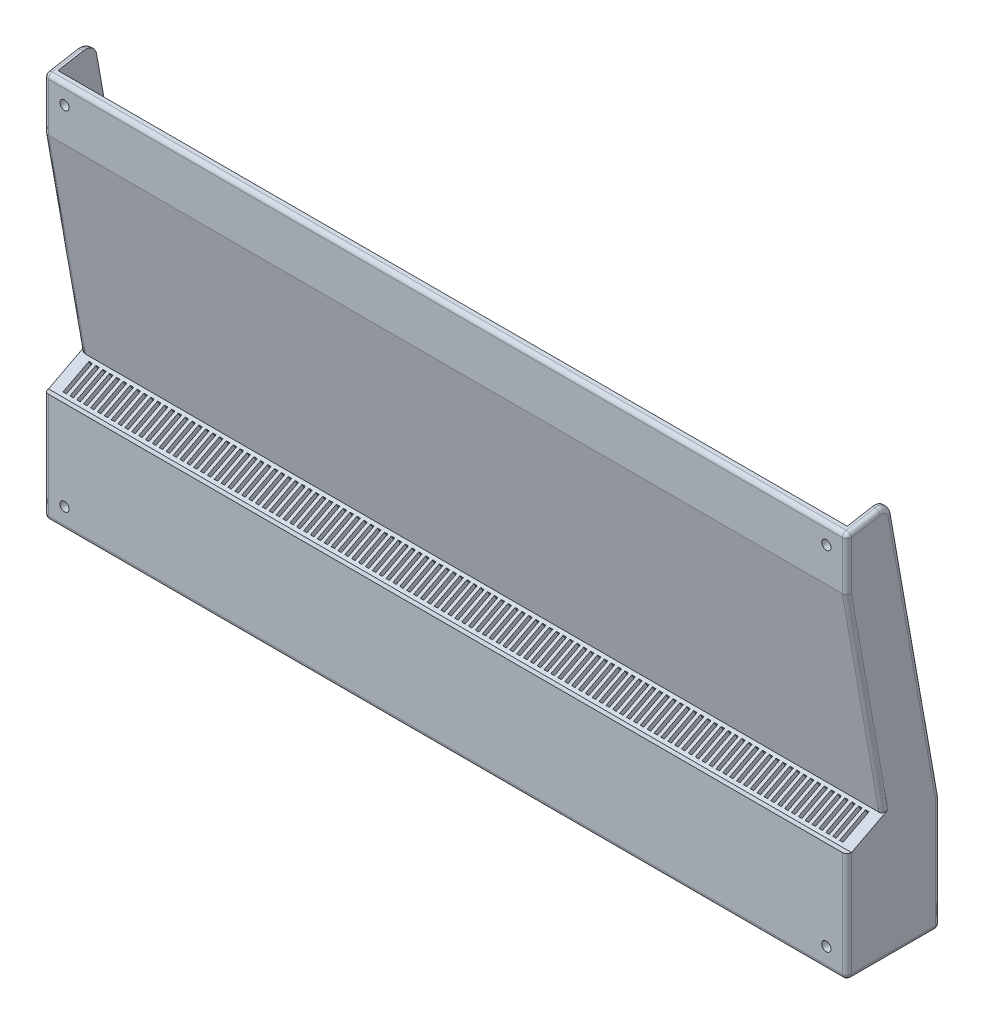
SolidWorks part; units mm, degrees
ref_plane "Front Plane" through (0, 0, 0) normal (0, 0, 1) x (1, 0, 0)
ref_plane "Top Plane" through (0, 0, 0) normal (0, 1, 0) x (1, 0, 0)
ref_plane "Right Plane" through (0, 0, 0) normal (1, 0, 0) x (0, 0, -1)
sketch "bottomplate" plane through (231.685, 0, 0) normal (1, 0, 0) x (0, 0, -1)
  line L0 (0, -72.0932) -> (-3.1401, -72.0932)
  line L1 (-3.1401, -72.0932) -> (-3.1401, 96.6415)
  line L2 (0, 97.1952) -> (11.0516, 99.1439) construction
  line L3 (-3.1401, 96.6415) -> (0, 97.1952)
  line L4 (0, 97.1952) -> (0, -72.0932)
  dimension "D1" = 0
extrude "B" add sketch "bottomplate" against normal up to surface (344.5411 mm away)
sketch "leftside" plane through (-112.8561, 0, 0) normal (-1, 0, 0) x (0, 0, 1)
  line L0 (3.1401, -72.0932) -> (-35.5061, -72.0932)
  line L2 (-37.5061, -70.0932) -> (-37.5061, -22.0932)
  line L3 (-37.5061, -22.0932) -> (-16.8439, 95.0881)
  line L5 (-11.0516, 99.1439) -> (3.1401, 96.6415)
  line L6 (3.1401, 96.6415) -> (3.1401, -72.0932)
  arc A0 (-35.5061, -72.0932) -> (-37.5061, -70.0932) centre (-35.5061, -70.0932) cw
  arc A1 (-11.0516, 99.1439) -> (-16.8439, 95.0881) centre (-11.9198, 94.2199) ccw
extrude "L" add sketch "leftside" along normal blind 3
sketch "rightside" plane through (231.685, 0, 0) normal (1, 0, 0) x (0, 0, -1)
  line L0 (-3.1401, -72.0932) -> (35.5061, -72.0932)
  line L2 (37.5061, -70.0932) -> (37.5061, -22.0932)
  line L3 (37.5061, -22.0932) -> (16.8439, 95.0881)
  line L5 (11.0516, 99.1439) -> (-3.1401, 96.6415)
  line L6 (-3.1401, 96.6415) -> (-3.1401, -72.0932)
  arc A0 (35.5061, -72.0932) -> (37.5061, -70.0932) centre (35.5061, -70.0932) ccw
  arc A1 (16.8439, 95.0881) -> (11.0516, 99.1439) centre (11.9198, 94.2199) ccw
extrude "R" add sketch "rightside" along normal blind 3
fillet "Fillet1" radius 2 2 edges at (59.4145, -72.0932, 3.1401) (59.4145, 96.6415, 3.1401)
fillet "Fillet2" radius 2 18 edges at (234.685, 36.4975, -27.175) (234.685, 98.3156, -14.7877) (234.685, 98.0384, -4.7821) (234.685, 96.2489, 2.6722) (234.685, -46.0932, -37.5061) (234.685, -71.5074, -36.9203) (234.685, -72.0932, -17.183) (234.685, -71.5074, 2.5543) (-115.8561, -46.0932, -37.5061) (-115.8561, -71.5074, -36.9203) (-115.8561, -72.0932, -17.183) (-115.8561, -71.5074, 2.5543) (-115.8561, 36.4975, -27.175) (-115.8561, 98.3156, -14.7877) (-115.8561, 98.0384, -4.7821) (-115.8561, 96.2489, 2.6722) (234.685, 12.4351, 3.1401) (-115.8561, 12.4351, 3.1401)
sketch "holes" plane through (0, 0, 3.1401) normal (0, 0, 1) x (1, 0, 0)
  circle A0 centre (225.685, -63.0932) radius 2
  circle A1 centre (225.685, 88.6699) radius 2
  circle A2 centre (-106.8561, 88.6699) radius 2
  circle A3 centre (-106.8561, -63.0932) radius 2
extrude "Cut-Extrude1" cut sketch "holes" against normal blind 6.5
sketch "Sketch3" plane through (-115.8561, 0, 0) normal (-1, 0, 0) x (0, 0, 1)
  line L0 (-16.9697, -14.7016) -> (-1.3669, 73.7862)
  line L1 (-16.9697, -14.7016) -> (1.1401, -24.0977)
  line L3 (1.1401, -70.0932) -> (1.1401, 94.9633) construction
  line L4 (-1.3669, 73.7862) -> (6.335, 73.7862)
  line L5 (6.335, 73.7862) -> (6.335, -24.0977)
  line L6 (6.335, -24.0977) -> (1.1401, -24.0977)
  line L7 (-5.393, 85.4533) -> (-22.5841, -12.0427) construction
  point P2 (1.1401, 73.822)
  point P10 (1.1401, -23.3058)
  point P11 (6.335, -24.0977)
  point P12 (1.1401, 73.824)
extrude "Cut-Extrude2" cut sketch "Sketch3" against normal up to surface (350.5411 mm away) up to face at (234.685, 20.8573, -15.9182)
sketch "Sketch7" plane through (0, 73.7862, 0) normal (0, -1, 0) x (1, 0, 0)
  line L0 (-112.8561, -1.3669) -> (-115.8561, -1.3669)
  line L1 (-115.8561, -1.3669) -> (-115.8561, 1.1401)
  line L3 (-113.8561, 3.1401) -> (232.685, 3.1401)
  line L4 (232.685, 1.1401) -> (232.685, 3.1401) construction
  line L6 (234.685, 1.1401) -> (234.685, -1.3669)
  line L7 (234.685, -1.3669) -> (231.685, -1.3669)
  line L8 (231.685, -1.3669) -> (231.685, 0)
  line L9 (231.685, 0) -> (-112.8561, 0)
  line L10 (-112.8561, 0) -> (-112.8561, -1.3669)
  arc A0 (234.685, 1.1401) -> (232.685, 3.1401) centre (232.685, 1.1401) ccw construction
  arc A1 (-115.8561, 1.1401) -> (-113.8561, 3.1401) centre (-113.8561, 1.1401) cw
  arc A2 (232.685, 3.1401) -> (234.685, 1.1401) centre (232.685, 1.1401) cw
extrude "Boss-Extrude1" add sketch "Sketch7" along direction (0, -0.9848, -0.1736) on the side of the normal blind 92.5
sketch "Sketch9" plane through (0, 0, 0) normal (0, 0, -1) x (-1, 0, 0)
  line L0 (112.8561, -23.5062) -> (-231.685, -23.5062)
  line L1 (-231.685, -23.5062) -> (-231.685, -26.5062)
  line L2 (-231.685, -72.0932) -> (-231.685, -23.5062) construction
  line L3 (-231.685, -26.5062) -> (112.8561, -26.5062)
  line L4 (112.8561, -72.0932) -> (112.8561, -23.5062) construction
  line L5 (112.8561, -26.5062) -> (112.8561, -23.5062)
  dimension "D1" = 3
extrude "Boss-Extrude2" add sketch "Sketch9" along direction (0, 0.4605, -0.8876) on the side of the normal up to surface (18.253 mm away) up to face at (59.4145, 28.2389, -8.0312)
sketch "Sketch10" plane through (0, -18.5205, -9.6093) normal (0, 0.8876, 0.4605) x (1, 0, 0)
  line L0 (-113.8561, 3.6402) -> (232.685, 3.6402) construction
  line L1 (-110.8561, -10.6101) -> (-109.3561, -10.6101)
  line L2 (-110.8561, -10.6101) -> (-110.8561, 2.1402)
  line L3 (-110.8561, 2.1402) -> (-109.3561, 2.1402)
  line L4 (-109.3561, -10.6101) -> (-109.3561, 2.1402)
  line L5 (234.685, -12.1101) -> (-115.8561, -12.1101) construction
  line L6 (-115.8561, 5.7046) -> (-115.8561, -12.1101) construction
  line L7 (-107.8561, -10.6101) -> (-107.8561, 2.1402)
  line L8 (-107.8561, -10.6101) -> (-106.3561, -10.6101)
  line L9 (-106.3561, -10.6101) -> (-106.3561, 2.1402)
  line L10 (-107.8561, 2.1402) -> (-106.3561, 2.1402)
  line L11 (-104.8561, -10.6101) -> (-104.8561, 2.1402)
  line L12 (-104.8561, -10.6101) -> (-103.3561, -10.6101)
  line L13 (-103.3561, -10.6101) -> (-103.3561, 2.1402)
  line L14 (-104.8561, 2.1402) -> (-103.3561, 2.1402)
  line L15 (-101.8561, -10.6101) -> (-101.8561, 2.1402)
  line L16 (-101.8561, -10.6101) -> (-100.3561, -10.6101)
  line L17 (-100.3561, -10.6101) -> (-100.3561, 2.1402)
  line L18 (-101.8561, 2.1402) -> (-100.3561, 2.1402)
  line L19 (-98.8561, -10.6101) -> (-98.8561, 2.1402)
  line L20 (-98.8561, -10.6101) -> (-97.3561, -10.6101)
  line L21 (-97.3561, -10.6101) -> (-97.3561, 2.1402)
  line L22 (-98.8561, 2.1402) -> (-97.3561, 2.1402)
  line L23 (-95.8561, -10.6101) -> (-95.8561, 2.1402)
  line L24 (-95.8561, -10.6101) -> (-94.3561, -10.6101)
  line L25 (-94.3561, -10.6101) -> (-94.3561, 2.1402)
  line L26 (-95.8561, 2.1402) -> (-94.3561, 2.1402)
  line L27 (-92.8561, -10.6101) -> (-92.8561, 2.1402)
  line L28 (-92.8561, -10.6101) -> (-91.3561, -10.6101)
  line L29 (-91.3561, -10.6101) -> (-91.3561, 2.1402)
  line L30 (-92.8561, 2.1402) -> (-91.3561, 2.1402)
  line L31 (-89.8561, -10.6101) -> (-89.8561, 2.1402)
  line L32 (-89.8561, -10.6101) -> (-88.3561, -10.6101)
  line L33 (-88.3561, -10.6101) -> (-88.3561, 2.1402)
  line L34 (-89.8561, 2.1402) -> (-88.3561, 2.1402)
  line L35 (-86.8561, -10.6101) -> (-86.8561, 2.1402)
  line L36 (-86.8561, -10.6101) -> (-85.3561, -10.6101)
  line L37 (-85.3561, -10.6101) -> (-85.3561, 2.1402)
  line L38 (-86.8561, 2.1402) -> (-85.3561, 2.1402)
  line L39 (-83.8561, -10.6101) -> (-83.8561, 2.1402)
  line L40 (-83.8561, -10.6101) -> (-82.3561, -10.6101)
  line L41 (-82.3561, -10.6101) -> (-82.3561, 2.1402)
  line L42 (-83.8561, 2.1402) -> (-82.3561, 2.1402)
  line L43 (-80.8561, -10.6101) -> (-80.8561, 2.1402)
  line L44 (-80.8561, -10.6101) -> (-79.3561, -10.6101)
  line L45 (-79.3561, -10.6101) -> (-79.3561, 2.1402)
  line L46 (-80.8561, 2.1402) -> (-79.3561, 2.1402)
  line L47 (-77.8561, -10.6101) -> (-77.8561, 2.1402)
  line L48 (-77.8561, -10.6101) -> (-76.3561, -10.6101)
  line L49 (-76.3561, -10.6101) -> (-76.3561, 2.1402)
  line L50 (-77.8561, 2.1402) -> (-76.3561, 2.1402)
  line L51 (-74.8561, -10.6101) -> (-74.8561, 2.1402)
  line L52 (-74.8561, -10.6101) -> (-73.3561, -10.6101)
  line L53 (-73.3561, -10.6101) -> (-73.3561, 2.1402)
  line L54 (-74.8561, 2.1402) -> (-73.3561, 2.1402)
  line L55 (-71.8561, -10.6101) -> (-71.8561, 2.1402)
  line L56 (-71.8561, -10.6101) -> (-70.3561, -10.6101)
  line L57 (-70.3561, -10.6101) -> (-70.3561, 2.1402)
  line L58 (-71.8561, 2.1402) -> (-70.3561, 2.1402)
  line L59 (-68.8561, -10.6101) -> (-68.8561, 2.1402)
  line L60 (-68.8561, -10.6101) -> (-67.3561, -10.6101)
  line L61 (-67.3561, -10.6101) -> (-67.3561, 2.1402)
  line L62 (-68.8561, 2.1402) -> (-67.3561, 2.1402)
  line L63 (-65.8561, -10.6101) -> (-65.8561, 2.1402)
  line L64 (-65.8561, -10.6101) -> (-64.3561, -10.6101)
  line L65 (-64.3561, -10.6101) -> (-64.3561, 2.1402)
  line L66 (-65.8561, 2.1402) -> (-64.3561, 2.1402)
  line L67 (-62.8561, -10.6101) -> (-62.8561, 2.1402)
  line L68 (-62.8561, -10.6101) -> (-61.3561, -10.6101)
  line L69 (-61.3561, -10.6101) -> (-61.3561, 2.1402)
  line L70 (-62.8561, 2.1402) -> (-61.3561, 2.1402)
  line L71 (-59.8561, -10.6101) -> (-59.8561, 2.1402)
  line L72 (-59.8561, -10.6101) -> (-58.3561, -10.6101)
  line L73 (-58.3561, -10.6101) -> (-58.3561, 2.1402)
  line L74 (-59.8561, 2.1402) -> (-58.3561, 2.1402)
  line L75 (-56.8561, -10.6101) -> (-56.8561, 2.1402)
  line L76 (-56.8561, -10.6101) -> (-55.3561, -10.6101)
  line L77 (-55.3561, -10.6101) -> (-55.3561, 2.1402)
  line L78 (-56.8561, 2.1402) -> (-55.3561, 2.1402)
  line L79 (-53.8561, -10.6101) -> (-53.8561, 2.1402)
  line L80 (-53.8561, -10.6101) -> (-52.3561, -10.6101)
  line L81 (-52.3561, -10.6101) -> (-52.3561, 2.1402)
  line L82 (-53.8561, 2.1402) -> (-52.3561, 2.1402)
  line L83 (-50.8561, -10.6101) -> (-50.8561, 2.1402)
  line L84 (-50.8561, -10.6101) -> (-49.3561, -10.6101)
  line L85 (-49.3561, -10.6101) -> (-49.3561, 2.1402)
  line L86 (-50.8561, 2.1402) -> (-49.3561, 2.1402)
  line L87 (-47.8561, -10.6101) -> (-47.8561, 2.1402)
  line L88 (-47.8561, -10.6101) -> (-46.3561, -10.6101)
  line L89 (-46.3561, -10.6101) -> (-46.3561, 2.1402)
  line L90 (-47.8561, 2.1402) -> (-46.3561, 2.1402)
  line L91 (-44.8561, -10.6101) -> (-44.8561, 2.1402)
  line L92 (-44.8561, -10.6101) -> (-43.3561, -10.6101)
  line L93 (-43.3561, -10.6101) -> (-43.3561, 2.1402)
  line L94 (-44.8561, 2.1402) -> (-43.3561, 2.1402)
  line L95 (-41.8561, -10.6101) -> (-41.8561, 2.1402)
  line L96 (-41.8561, -10.6101) -> (-40.3561, -10.6101)
  line L97 (-40.3561, -10.6101) -> (-40.3561, 2.1402)
  line L98 (-41.8561, 2.1402) -> (-40.3561, 2.1402)
  line L99 (-38.8561, -10.6101) -> (-38.8561, 2.1402)
  line L100 (-38.8561, -10.6101) -> (-37.3561, -10.6101)
  line L101 (-37.3561, -10.6101) -> (-37.3561, 2.1402)
  line L102 (-38.8561, 2.1402) -> (-37.3561, 2.1402)
  line L103 (-35.8561, -10.6101) -> (-35.8561, 2.1402)
  line L104 (-35.8561, -10.6101) -> (-34.3561, -10.6101)
  line L105 (-34.3561, -10.6101) -> (-34.3561, 2.1402)
  line L106 (-35.8561, 2.1402) -> (-34.3561, 2.1402)
  line L107 (-32.8561, -10.6101) -> (-32.8561, 2.1402)
  line L108 (-32.8561, -10.6101) -> (-31.3561, -10.6101)
  line L109 (-31.3561, -10.6101) -> (-31.3561, 2.1402)
  line L110 (-32.8561, 2.1402) -> (-31.3561, 2.1402)
  line L111 (-29.8561, -10.6101) -> (-29.8561, 2.1402)
  line L112 (-29.8561, -10.6101) -> (-28.3561, -10.6101)
  line L113 (-28.3561, -10.6101) -> (-28.3561, 2.1402)
  line L114 (-29.8561, 2.1402) -> (-28.3561, 2.1402)
  line L115 (-26.8561, -10.6101) -> (-26.8561, 2.1402)
  line L116 (-26.8561, -10.6101) -> (-25.3561, -10.6101)
  line L117 (-25.3561, -10.6101) -> (-25.3561, 2.1402)
  line L118 (-26.8561, 2.1402) -> (-25.3561, 2.1402)
  line L119 (-23.8561, -10.6101) -> (-23.8561, 2.1402)
  line L120 (-23.8561, -10.6101) -> (-22.3561, -10.6101)
  line L121 (-22.3561, -10.6101) -> (-22.3561, 2.1402)
  line L122 (-23.8561, 2.1402) -> (-22.3561, 2.1402)
  line L123 (-20.8561, -10.6101) -> (-20.8561, 2.1402)
  line L124 (-20.8561, -10.6101) -> (-19.3561, -10.6101)
  line L125 (-19.3561, -10.6101) -> (-19.3561, 2.1402)
  line L126 (-20.8561, 2.1402) -> (-19.3561, 2.1402)
  line L127 (-17.8561, -10.6101) -> (-17.8561, 2.1402)
  line L128 (-17.8561, -10.6101) -> (-16.3561, -10.6101)
  line L129 (-16.3561, -10.6101) -> (-16.3561, 2.1402)
  line L130 (-17.8561, 2.1402) -> (-16.3561, 2.1402)
  line L131 (-14.8561, -10.6101) -> (-14.8561, 2.1402)
  line L132 (-14.8561, -10.6101) -> (-13.3561, -10.6101)
  line L133 (-13.3561, -10.6101) -> (-13.3561, 2.1402)
  line L134 (-14.8561, 2.1402) -> (-13.3561, 2.1402)
  line L135 (-11.8561, -10.6101) -> (-11.8561, 2.1402)
  line L136 (-11.8561, -10.6101) -> (-10.3561, -10.6101)
  line L137 (-10.3561, -10.6101) -> (-10.3561, 2.1402)
  line L138 (-11.8561, 2.1402) -> (-10.3561, 2.1402)
  line L139 (-8.8561, -10.6101) -> (-8.8561, 2.1402)
  line L140 (-8.8561, -10.6101) -> (-7.3561, -10.6101)
  line L141 (-7.3561, -10.6101) -> (-7.3561, 2.1402)
  line L142 (-8.8561, 2.1402) -> (-7.3561, 2.1402)
  line L143 (-5.8561, -10.6101) -> (-5.8561, 2.1402)
  line L144 (-5.8561, -10.6101) -> (-4.3561, -10.6101)
  line L145 (-4.3561, -10.6101) -> (-4.3561, 2.1402)
  line L146 (-5.8561, 2.1402) -> (-4.3561, 2.1402)
  line L147 (-2.8561, -10.6101) -> (-2.8561, 2.1402)
  line L148 (-2.8561, -10.6101) -> (-1.3561, -10.6101)
  line L149 (-1.3561, -10.6101) -> (-1.3561, 2.1402)
  line L150 (-2.8561, 2.1402) -> (-1.3561, 2.1402)
  line L151 (0.1439, -10.6101) -> (0.1439, 2.1402)
  line L152 (0.1439, -10.6101) -> (1.6439, -10.6101)
  line L153 (1.6439, -10.6101) -> (1.6439, 2.1402)
  line L154 (0.1439, 2.1402) -> (1.6439, 2.1402)
  line L155 (3.1439, -10.6101) -> (3.1439, 2.1402)
  line L156 (3.1439, -10.6101) -> (4.6439, -10.6101)
  line L157 (4.6439, -10.6101) -> (4.6439, 2.1402)
  line L158 (3.1439, 2.1402) -> (4.6439, 2.1402)
  line L159 (6.1439, -10.6101) -> (6.1439, 2.1402)
  line L160 (6.1439, -10.6101) -> (7.6439, -10.6101)
  line L161 (7.6439, -10.6101) -> (7.6439, 2.1402)
  line L162 (6.1439, 2.1402) -> (7.6439, 2.1402)
  line L163 (9.1439, -10.6101) -> (9.1439, 2.1402)
  line L164 (9.1439, -10.6101) -> (10.6439, -10.6101)
  line L165 (10.6439, -10.6101) -> (10.6439, 2.1402)
  line L166 (9.1439, 2.1402) -> (10.6439, 2.1402)
  line L167 (12.1439, -10.6101) -> (12.1439, 2.1402)
  line L168 (12.1439, -10.6101) -> (13.6439, -10.6101)
  line L169 (13.6439, -10.6101) -> (13.6439, 2.1402)
  line L170 (12.1439, 2.1402) -> (13.6439, 2.1402)
  line L171 (15.1439, -10.6101) -> (15.1439, 2.1402)
  line L172 (15.1439, -10.6101) -> (16.6439, -10.6101)
  line L173 (16.6439, -10.6101) -> (16.6439, 2.1402)
  line L174 (15.1439, 2.1402) -> (16.6439, 2.1402)
  line L175 (18.1439, -10.6101) -> (18.1439, 2.1402)
  line L176 (18.1439, -10.6101) -> (19.6439, -10.6101)
  line L177 (19.6439, -10.6101) -> (19.6439, 2.1402)
  line L178 (18.1439, 2.1402) -> (19.6439, 2.1402)
  line L179 (21.1439, -10.6101) -> (21.1439, 2.1402)
  line L180 (21.1439, -10.6101) -> (22.6439, -10.6101)
  line L181 (22.6439, -10.6101) -> (22.6439, 2.1402)
  line L182 (21.1439, 2.1402) -> (22.6439, 2.1402)
  line L183 (24.1439, -10.6101) -> (24.1439, 2.1402)
  line L184 (24.1439, -10.6101) -> (25.6439, -10.6101)
  line L185 (25.6439, -10.6101) -> (25.6439, 2.1402)
  line L186 (24.1439, 2.1402) -> (25.6439, 2.1402)
  line L187 (27.1439, -10.6101) -> (27.1439, 2.1402)
  line L188 (27.1439, -10.6101) -> (28.6439, -10.6101)
  line L189 (28.6439, -10.6101) -> (28.6439, 2.1402)
  line L190 (27.1439, 2.1402) -> (28.6439, 2.1402)
  line L191 (30.1439, -10.6101) -> (30.1439, 2.1402)
  line L192 (30.1439, -10.6101) -> (31.6439, -10.6101)
  line L193 (31.6439, -10.6101) -> (31.6439, 2.1402)
  line L194 (30.1439, 2.1402) -> (31.6439, 2.1402)
  line L195 (33.1439, -10.6101) -> (33.1439, 2.1402)
  line L196 (33.1439, -10.6101) -> (34.6439, -10.6101)
  line L197 (34.6439, -10.6101) -> (34.6439, 2.1402)
  line L198 (33.1439, 2.1402) -> (34.6439, 2.1402)
  line L199 (36.1439, -10.6101) -> (36.1439, 2.1402)
  line L200 (36.1439, -10.6101) -> (37.6439, -10.6101)
  line L201 (37.6439, -10.6101) -> (37.6439, 2.1402)
  line L202 (36.1439, 2.1402) -> (37.6439, 2.1402)
  line L203 (39.1439, -10.6101) -> (39.1439, 2.1402)
  line L204 (39.1439, -10.6101) -> (40.6439, -10.6101)
  line L205 (40.6439, -10.6101) -> (40.6439, 2.1402)
  line L206 (39.1439, 2.1402) -> (40.6439, 2.1402)
  line L207 (42.1439, -10.6101) -> (42.1439, 2.1402)
  line L208 (42.1439, -10.6101) -> (43.6439, -10.6101)
  line L209 (43.6439, -10.6101) -> (43.6439, 2.1402)
  line L210 (42.1439, 2.1402) -> (43.6439, 2.1402)
  line L211 (45.1439, -10.6101) -> (45.1439, 2.1402)
  line L212 (45.1439, -10.6101) -> (46.6439, -10.6101)
  line L213 (46.6439, -10.6101) -> (46.6439, 2.1402)
  line L214 (45.1439, 2.1402) -> (46.6439, 2.1402)
  line L215 (48.1439, -10.6101) -> (48.1439, 2.1402)
  line L216 (48.1439, -10.6101) -> (49.6439, -10.6101)
  line L217 (49.6439, -10.6101) -> (49.6439, 2.1402)
  line L218 (48.1439, 2.1402) -> (49.6439, 2.1402)
  line L219 (51.1439, -10.6101) -> (51.1439, 2.1402)
  line L220 (51.1439, -10.6101) -> (52.6439, -10.6101)
  line L221 (52.6439, -10.6101) -> (52.6439, 2.1402)
  line L222 (51.1439, 2.1402) -> (52.6439, 2.1402)
  line L223 (54.1439, -10.6101) -> (54.1439, 2.1402)
  line L224 (54.1439, -10.6101) -> (55.6439, -10.6101)
  line L225 (55.6439, -10.6101) -> (55.6439, 2.1402)
  line L226 (54.1439, 2.1402) -> (55.6439, 2.1402)
  line L227 (57.1439, -10.6101) -> (57.1439, 2.1402)
  line L228 (57.1439, -10.6101) -> (58.6439, -10.6101)
  line L229 (58.6439, -10.6101) -> (58.6439, 2.1402)
  line L230 (57.1439, 2.1402) -> (58.6439, 2.1402)
  line L231 (60.1439, -10.6101) -> (60.1439, 2.1402)
  line L232 (60.1439, -10.6101) -> (61.6439, -10.6101)
  line L233 (61.6439, -10.6101) -> (61.6439, 2.1402)
  line L234 (60.1439, 2.1402) -> (61.6439, 2.1402)
  line L235 (63.1439, -10.6101) -> (63.1439, 2.1402)
  line L236 (63.1439, -10.6101) -> (64.6439, -10.6101)
  line L237 (64.6439, -10.6101) -> (64.6439, 2.1402)
  line L238 (63.1439, 2.1402) -> (64.6439, 2.1402)
  line L239 (66.1439, -10.6101) -> (66.1439, 2.1402)
  line L240 (66.1439, -10.6101) -> (67.6439, -10.6101)
  line L241 (67.6439, -10.6101) -> (67.6439, 2.1402)
  line L242 (66.1439, 2.1402) -> (67.6439, 2.1402)
  line L243 (69.1439, -10.6101) -> (69.1439, 2.1402)
  line L244 (69.1439, -10.6101) -> (70.6439, -10.6101)
  line L245 (70.6439, -10.6101) -> (70.6439, 2.1402)
  line L246 (69.1439, 2.1402) -> (70.6439, 2.1402)
  line L247 (72.1439, -10.6101) -> (72.1439, 2.1402)
  line L248 (72.1439, -10.6101) -> (73.6439, -10.6101)
  line L249 (73.6439, -10.6101) -> (73.6439, 2.1402)
  line L250 (72.1439, 2.1402) -> (73.6439, 2.1402)
  line L251 (75.1439, -10.6101) -> (75.1439, 2.1402)
  line L252 (75.1439, -10.6101) -> (76.6439, -10.6101)
  line L253 (76.6439, -10.6101) -> (76.6439, 2.1402)
  line L254 (75.1439, 2.1402) -> (76.6439, 2.1402)
  line L255 (78.1439, -10.6101) -> (78.1439, 2.1402)
  line L256 (78.1439, -10.6101) -> (79.6439, -10.6101)
  line L257 (79.6439, -10.6101) -> (79.6439, 2.1402)
  line L258 (78.1439, 2.1402) -> (79.6439, 2.1402)
  line L259 (81.1439, -10.6101) -> (81.1439, 2.1402)
  line L260 (81.1439, -10.6101) -> (82.6439, -10.6101)
  line L261 (82.6439, -10.6101) -> (82.6439, 2.1402)
  line L262 (81.1439, 2.1402) -> (82.6439, 2.1402)
  line L263 (84.1439, -10.6101) -> (84.1439, 2.1402)
  line L264 (84.1439, -10.6101) -> (85.6439, -10.6101)
  line L265 (85.6439, -10.6101) -> (85.6439, 2.1402)
  line L266 (84.1439, 2.1402) -> (85.6439, 2.1402)
  line L267 (87.1439, -10.6101) -> (87.1439, 2.1402)
  line L268 (87.1439, -10.6101) -> (88.6439, -10.6101)
  line L269 (88.6439, -10.6101) -> (88.6439, 2.1402)
  line L270 (87.1439, 2.1402) -> (88.6439, 2.1402)
  line L271 (90.1439, -10.6101) -> (90.1439, 2.1402)
  line L272 (90.1439, -10.6101) -> (91.6439, -10.6101)
  line L273 (91.6439, -10.6101) -> (91.6439, 2.1402)
  line L274 (90.1439, 2.1402) -> (91.6439, 2.1402)
  line L275 (93.1439, -10.6101) -> (93.1439, 2.1402)
  line L276 (93.1439, -10.6101) -> (94.6439, -10.6101)
  line L277 (94.6439, -10.6101) -> (94.6439, 2.1402)
  line L278 (93.1439, 2.1402) -> (94.6439, 2.1402)
  line L279 (96.1439, -10.6101) -> (96.1439, 2.1402)
  line L280 (96.1439, -10.6101) -> (97.6439, -10.6101)
  line L281 (97.6439, -10.6101) -> (97.6439, 2.1402)
  line L282 (96.1439, 2.1402) -> (97.6439, 2.1402)
  line L283 (99.1439, -10.6101) -> (99.1439, 2.1402)
  line L284 (99.1439, -10.6101) -> (100.6439, -10.6101)
  line L285 (100.6439, -10.6101) -> (100.6439, 2.1402)
  line L286 (99.1439, 2.1402) -> (100.6439, 2.1402)
  line L287 (102.1439, -10.6101) -> (102.1439, 2.1402)
  line L288 (102.1439, -10.6101) -> (103.6439, -10.6101)
  line L289 (103.6439, -10.6101) -> (103.6439, 2.1402)
  line L290 (102.1439, 2.1402) -> (103.6439, 2.1402)
  line L291 (105.1439, -10.6101) -> (105.1439, 2.1402)
  line L292 (105.1439, -10.6101) -> (106.6439, -10.6101)
  line L293 (106.6439, -10.6101) -> (106.6439, 2.1402)
  line L294 (105.1439, 2.1402) -> (106.6439, 2.1402)
  line L295 (108.1439, -10.6101) -> (108.1439, 2.1402)
  line L296 (108.1439, -10.6101) -> (109.6439, -10.6101)
  line L297 (109.6439, -10.6101) -> (109.6439, 2.1402)
  line L298 (108.1439, 2.1402) -> (109.6439, 2.1402)
  line L299 (111.1439, -10.6101) -> (111.1439, 2.1402)
  line L300 (111.1439, -10.6101) -> (112.6439, -10.6101)
  line L301 (112.6439, -10.6101) -> (112.6439, 2.1402)
  line L302 (111.1439, 2.1402) -> (112.6439, 2.1402)
  line L303 (114.1439, -10.6101) -> (114.1439, 2.1402)
  line L304 (114.1439, -10.6101) -> (115.6439, -10.6101)
  line L305 (115.6439, -10.6101) -> (115.6439, 2.1402)
  line L306 (114.1439, 2.1402) -> (115.6439, 2.1402)
  line L307 (117.1439, -10.6101) -> (117.1439, 2.1402)
  line L308 (117.1439, -10.6101) -> (118.6439, -10.6101)
  line L309 (118.6439, -10.6101) -> (118.6439, 2.1402)
  line L310 (117.1439, 2.1402) -> (118.6439, 2.1402)
  line L311 (120.1439, -10.6101) -> (120.1439, 2.1402)
  line L312 (120.1439, -10.6101) -> (121.6439, -10.6101)
  line L313 (121.6439, -10.6101) -> (121.6439, 2.1402)
  line L314 (120.1439, 2.1402) -> (121.6439, 2.1402)
  line L315 (123.1439, -10.6101) -> (123.1439, 2.1402)
  line L316 (123.1439, -10.6101) -> (124.6439, -10.6101)
  line L317 (124.6439, -10.6101) -> (124.6439, 2.1402)
  line L318 (123.1439, 2.1402) -> (124.6439, 2.1402)
  line L319 (126.1439, -10.6101) -> (126.1439, 2.1402)
  line L320 (126.1439, -10.6101) -> (127.6439, -10.6101)
  line L321 (127.6439, -10.6101) -> (127.6439, 2.1402)
  line L322 (126.1439, 2.1402) -> (127.6439, 2.1402)
  line L323 (129.1439, -10.6101) -> (129.1439, 2.1402)
  line L324 (129.1439, -10.6101) -> (130.6439, -10.6101)
  line L325 (130.6439, -10.6101) -> (130.6439, 2.1402)
  line L326 (129.1439, 2.1402) -> (130.6439, 2.1402)
  line L327 (132.1439, -10.6101) -> (132.1439, 2.1402)
  line L328 (132.1439, -10.6101) -> (133.6439, -10.6101)
  line L329 (133.6439, -10.6101) -> (133.6439, 2.1402)
  line L330 (132.1439, 2.1402) -> (133.6439, 2.1402)
  line L331 (135.1439, -10.6101) -> (135.1439, 2.1402)
  line L332 (135.1439, -10.6101) -> (136.6439, -10.6101)
  line L333 (136.6439, -10.6101) -> (136.6439, 2.1402)
  line L334 (135.1439, 2.1402) -> (136.6439, 2.1402)
  line L335 (138.1439, -10.6101) -> (138.1439, 2.1402)
  line L336 (138.1439, -10.6101) -> (139.6439, -10.6101)
  line L337 (139.6439, -10.6101) -> (139.6439, 2.1402)
  line L338 (138.1439, 2.1402) -> (139.6439, 2.1402)
  line L339 (141.1439, -10.6101) -> (141.1439, 2.1402)
  line L340 (141.1439, -10.6101) -> (142.6439, -10.6101)
  line L341 (142.6439, -10.6101) -> (142.6439, 2.1402)
  line L342 (141.1439, 2.1402) -> (142.6439, 2.1402)
  line L343 (144.1439, -10.6101) -> (144.1439, 2.1402)
  line L344 (144.1439, -10.6101) -> (145.6439, -10.6101)
  line L345 (145.6439, -10.6101) -> (145.6439, 2.1402)
  line L346 (144.1439, 2.1402) -> (145.6439, 2.1402)
  line L347 (147.1439, -10.6101) -> (147.1439, 2.1402)
  line L348 (147.1439, -10.6101) -> (148.6439, -10.6101)
  line L349 (148.6439, -10.6101) -> (148.6439, 2.1402)
  line L350 (147.1439, 2.1402) -> (148.6439, 2.1402)
  line L351 (150.1439, -10.6101) -> (150.1439, 2.1402)
  line L352 (150.1439, -10.6101) -> (151.6439, -10.6101)
  line L353 (151.6439, -10.6101) -> (151.6439, 2.1402)
  line L354 (150.1439, 2.1402) -> (151.6439, 2.1402)
  line L355 (153.1439, -10.6101) -> (153.1439, 2.1402)
  line L356 (153.1439, -10.6101) -> (154.6439, -10.6101)
  line L357 (154.6439, -10.6101) -> (154.6439, 2.1402)
  line L358 (153.1439, 2.1402) -> (154.6439, 2.1402)
  line L359 (156.1439, -10.6101) -> (156.1439, 2.1402)
  line L360 (156.1439, -10.6101) -> (157.6439, -10.6101)
  line L361 (157.6439, -10.6101) -> (157.6439, 2.1402)
  line L362 (156.1439, 2.1402) -> (157.6439, 2.1402)
  line L363 (159.1439, -10.6101) -> (159.1439, 2.1402)
  line L364 (159.1439, -10.6101) -> (160.6439, -10.6101)
  line L365 (160.6439, -10.6101) -> (160.6439, 2.1402)
  line L366 (159.1439, 2.1402) -> (160.6439, 2.1402)
  line L367 (162.1439, -10.6101) -> (162.1439, 2.1402)
  line L368 (162.1439, -10.6101) -> (163.6439, -10.6101)
  line L369 (163.6439, -10.6101) -> (163.6439, 2.1402)
  line L370 (162.1439, 2.1402) -> (163.6439, 2.1402)
  line L371 (165.1439, -10.6101) -> (165.1439, 2.1402)
  line L372 (165.1439, -10.6101) -> (166.6439, -10.6101)
  line L373 (166.6439, -10.6101) -> (166.6439, 2.1402)
  line L374 (165.1439, 2.1402) -> (166.6439, 2.1402)
  line L375 (168.1439, -10.6101) -> (168.1439, 2.1402)
  line L376 (168.1439, -10.6101) -> (169.6439, -10.6101)
  line L377 (169.6439, -10.6101) -> (169.6439, 2.1402)
  line L378 (168.1439, 2.1402) -> (169.6439, 2.1402)
  line L379 (171.1439, -10.6101) -> (171.1439, 2.1402)
  line L380 (171.1439, -10.6101) -> (172.6439, -10.6101)
  line L381 (172.6439, -10.6101) -> (172.6439, 2.1402)
  line L382 (171.1439, 2.1402) -> (172.6439, 2.1402)
  line L383 (174.1439, -10.6101) -> (174.1439, 2.1402)
  line L384 (174.1439, -10.6101) -> (175.6439, -10.6101)
  line L385 (175.6439, -10.6101) -> (175.6439, 2.1402)
  line L386 (174.1439, 2.1402) -> (175.6439, 2.1402)
  line L387 (177.1439, -10.6101) -> (177.1439, 2.1402)
  line L388 (177.1439, -10.6101) -> (178.6439, -10.6101)
  line L389 (178.6439, -10.6101) -> (178.6439, 2.1402)
  line L390 (177.1439, 2.1402) -> (178.6439, 2.1402)
  line L391 (180.1439, -10.6101) -> (180.1439, 2.1402)
  line L392 (180.1439, -10.6101) -> (181.6439, -10.6101)
  line L393 (181.6439, -10.6101) -> (181.6439, 2.1402)
  line L394 (180.1439, 2.1402) -> (181.6439, 2.1402)
  line L395 (183.1439, -10.6101) -> (183.1439, 2.1402)
  line L396 (183.1439, -10.6101) -> (184.6439, -10.6101)
  line L397 (184.6439, -10.6101) -> (184.6439, 2.1402)
  line L398 (183.1439, 2.1402) -> (184.6439, 2.1402)
  line L399 (186.1439, -10.6101) -> (186.1439, 2.1402)
  line L400 (186.1439, -10.6101) -> (187.6439, -10.6101)
  line L401 (187.6439, -10.6101) -> (187.6439, 2.1402)
  line L402 (186.1439, 2.1402) -> (187.6439, 2.1402)
  line L403 (189.1439, -10.6101) -> (189.1439, 2.1402)
  line L404 (189.1439, -10.6101) -> (190.6439, -10.6101)
  line L405 (190.6439, -10.6101) -> (190.6439, 2.1402)
  line L406 (189.1439, 2.1402) -> (190.6439, 2.1402)
  line L407 (192.1439, -10.6101) -> (192.1439, 2.1402)
  line L408 (192.1439, -10.6101) -> (193.6439, -10.6101)
  line L409 (193.6439, -10.6101) -> (193.6439, 2.1402)
  line L410 (192.1439, 2.1402) -> (193.6439, 2.1402)
  line L411 (195.1439, -10.6101) -> (195.1439, 2.1402)
  line L412 (195.1439, -10.6101) -> (196.6439, -10.6101)
  line L413 (196.6439, -10.6101) -> (196.6439, 2.1402)
  line L414 (195.1439, 2.1402) -> (196.6439, 2.1402)
  line L415 (198.1439, -10.6101) -> (198.1439, 2.1402)
  line L416 (198.1439, -10.6101) -> (199.6439, -10.6101)
  line L417 (199.6439, -10.6101) -> (199.6439, 2.1402)
  line L418 (198.1439, 2.1402) -> (199.6439, 2.1402)
  line L419 (201.1439, -10.6101) -> (201.1439, 2.1402)
  line L420 (201.1439, -10.6101) -> (202.6439, -10.6101)
  line L421 (202.6439, -10.6101) -> (202.6439, 2.1402)
  line L422 (201.1439, 2.1402) -> (202.6439, 2.1402)
  line L423 (204.1439, -10.6101) -> (204.1439, 2.1402)
  line L424 (204.1439, -10.6101) -> (205.6439, -10.6101)
  line L425 (205.6439, -10.6101) -> (205.6439, 2.1402)
  line L426 (204.1439, 2.1402) -> (205.6439, 2.1402)
  line L427 (207.1439, -10.6101) -> (207.1439, 2.1402)
  line L428 (207.1439, -10.6101) -> (208.6439, -10.6101)
  line L429 (208.6439, -10.6101) -> (208.6439, 2.1402)
  line L430 (207.1439, 2.1402) -> (208.6439, 2.1402)
  line L431 (210.1439, -10.6101) -> (210.1439, 2.1402)
  line L432 (210.1439, -10.6101) -> (211.6439, -10.6101)
  line L433 (211.6439, -10.6101) -> (211.6439, 2.1402)
  line L434 (210.1439, 2.1402) -> (211.6439, 2.1402)
  line L435 (213.1439, -10.6101) -> (213.1439, 2.1402)
  line L436 (213.1439, -10.6101) -> (214.6439, -10.6101)
  line L437 (214.6439, -10.6101) -> (214.6439, 2.1402)
  line L438 (213.1439, 2.1402) -> (214.6439, 2.1402)
  line L439 (216.1439, -10.6101) -> (216.1439, 2.1402)
  line L440 (216.1439, -10.6101) -> (217.6439, -10.6101)
  line L441 (217.6439, -10.6101) -> (217.6439, 2.1402)
  line L442 (216.1439, 2.1402) -> (217.6439, 2.1402)
  line L443 (219.1439, -10.6101) -> (219.1439, 2.1402)
  line L444 (219.1439, -10.6101) -> (220.6439, -10.6101)
  line L445 (220.6439, -10.6101) -> (220.6439, 2.1402)
  line L446 (219.1439, 2.1402) -> (220.6439, 2.1402)
  line L447 (222.1439, -10.6101) -> (222.1439, 2.1402)
  line L448 (222.1439, -10.6101) -> (223.6439, -10.6101)
  line L449 (223.6439, -10.6101) -> (223.6439, 2.1402)
  line L450 (222.1439, 2.1402) -> (223.6439, 2.1402)
  line L451 (225.1439, -10.6101) -> (225.1439, 2.1402)
  line L452 (225.1439, -10.6101) -> (226.6439, -10.6101)
  line L453 (226.6439, -10.6101) -> (226.6439, 2.1402)
  line L454 (225.1439, 2.1402) -> (226.6439, 2.1402)
  line L455 (228.1439, -10.6101) -> (228.1439, 2.1402)
  line L456 (228.1439, -10.6101) -> (229.6439, -10.6101)
  line L457 (229.6439, -10.6101) -> (229.6439, 2.1402)
  line L458 (228.1439, 2.1402) -> (229.6439, 2.1402)
  dimension "D1" = 1.5
  dimension "D2" = 1.5
  dimension "D3" = 1.5
  dimension "D4" = 5
  dimension "D5" = 114
extrude "Cut-Extrude3" cut sketch "Sketch10" against normal up to surface (2.6629 mm away) up to face at (59.4145, -22.3031, -8.101)
